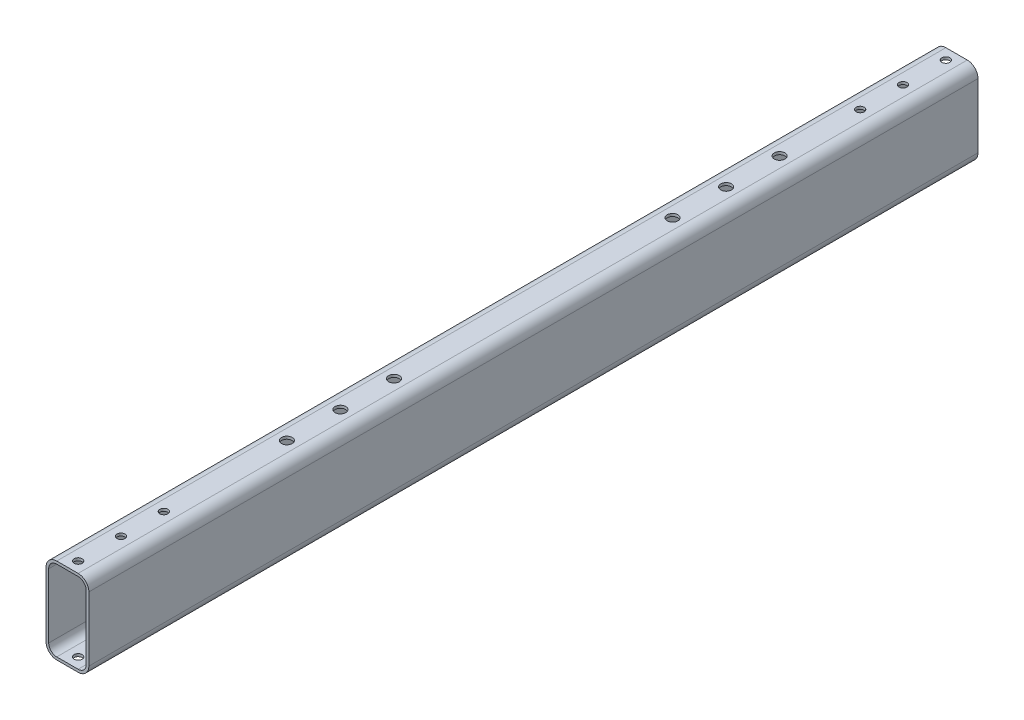
SolidWorks part; units mm, degrees
material "6061-T6 (SS)"
ref_plane "Front Plane" through (0, 0, 0) normal (0, 0, 1) x (1, 0, 0)
ref_plane "Top Plane" through (0, 0, 0) normal (0, 1, 0) x (1, 0, 0)
ref_plane "Right Plane" through (0, 0, 0) normal (1, 0, 0) x (0, 0, -1)
sketch "Sketch1" plane through (0, 0, 0) normal (0, 0, 1) x (1, 0, 0)
  line L1 (-6.35, -25.4) -> (6.35, -25.4)
  line L2 (-12.7, -19.05) -> (-12.7, 19.05)
  line L3 (-6.35, 25.4) -> (6.35, 25.4)
  line L4 (12.7, -19.05) -> (12.7, 19.05)
  line L5 (-12.7, -25.4) -> (12.7, 25.4) construction
  line L6 (-12.7, 25.4) -> (12.7, -25.4) construction
  arc A0 (-12.7, -19.05) -> (-6.35, -25.4) centre (-6.35, -19.05) ccw
  arc A1 (6.35, -25.4) -> (12.7, -19.05) centre (6.35, -19.05) ccw
  arc A2 (6.35, 25.4) -> (12.7, 19.05) centre (6.35, 19.05) cw
  arc A3 (-12.7, 19.05) -> (-6.35, 25.4) centre (-6.35, 19.05) cw
  point P0 (0, 0)
  dimension "D3" = 6.35
  dimension "D1" = 50.8
  dimension "D2" = 25.4
extrude "Extrude-Thin1" add sketch "Sketch1" along normal blind 527.05 thin thin type one direction reverse wall 1.5875
hole_wizard "3/16 (0.1875) Diameter Hole1" positions "3DSketch1" profile "Sketch3" hole size "3/16" standard "ANSI Inch" end condition through all
sketch3d "3DSketch1"
  line L1 (6.35, 25.4, 0) -> (-6.35, 25.4, 0) construction
  line L6 (0, 25.4, 527.05) -> (0, 25.4, 0) construction
  line L7 (6.35, 25.4, 527.05) -> (-6.35, 25.4, 527.05) construction
  point P57 (0, 25.4, 6.35)
  point P59 (0, 25.4, 31.75)
  point P61 (0, 25.4, 57.15)
  point P63 (0, 25.4, 495.3)
  point P65 (0, 25.4, 469.9)
  point P67 (0, 25.4, 520.7)
  dimension "D1" = 25.4
  dimension "D2" = 25.4
  dimension "D3" = 6.35
  dimension "D4" = 25.4
  dimension "D5" = 25.4
  dimension "D6" = 6.35
sketch "Sketch3" plane through (0, 25.4, 520.7) normal (1, 0, 0) x (0, 0, 1)
  line L0 (0, 0) -> (0, 50.8)
  line L1 (0, 50.8) -> (2.3812, 50.8)
  line L2 (2.3812, 50.8) -> (2.3812, 0)
  line L5 (2.3812, 0) -> (0, 0)
  line L11 (0, -6.35) -> (0, 107.95) construction
  dimension "Thru Hole Dia." = 4.7625
  dimension "Thru Hole Depth" = 50.8
hole_wizard "3/16 (0.195) Diameter Hole1" positions "Sketch4" profile "Sketch5" hole size "3/16" standard "ANSI Inch" end condition up to next
sketch "Sketch4" plane through (0, -25.4, 0) normal (0, -1, 0) x (-1, 0, 0)
  point P28 (3.175, -69.85)
  point P31 (-3.175, -95.25)
  point P34 (3.175, -120.65)
  point P37 (-3.175, -146.05)
  point P40 (3.175, -171.45)
  point P43 (3.175, -323.85)
  point P46 (-3.175, -349.25)
  point P49 (3.175, -374.65)
  point P52 (-3.175, -400.05)
  point P55 (3.175, -425.45)
sketch "Sketch5" plane through (-3.175, -25.4, 69.85) normal (1, 0, 0) x (0, 0, -1)
  line L0 (0, 0) -> (0, 1.5875)
  line L1 (0, 1.5875) -> (2.4765, 1.5875)
  line L2 (2.4765, 1.5875) -> (2.4765, 0)
  line L5 (2.4765, 0) -> (0, 0)
  line L11 (0, -6.35) -> (0, 107.95) construction
  dimension "Thru Hole Dia." = 4.953
  dimension "Thru Hole Depth" = 1.5875
hole_wizard "1/4 (0.25) Diameter Hole1" positions "Sketch7" profile "Sketch6" hole size "1/4" standard "ANSI Inch"
sketch "Sketch7" plane through (0, 25.4, 0) normal (0, 1, 0) x (1, 0, 0)
  point P0 (0, -104.85)
  point P3 (0, -136.6)
  point P6 (0, -168.35)
  point P9 (0, -396.9748)
  point P12 (0, -365.2248)
  point P15 (0, -333.4748)
sketch "Sketch6" plane through (0, 25.4, 104.85) normal (1, 0, 0) x (0, 0, 1)
  line L0 (0, 0) -> (0, 27.3077)
  line L1 (0, 27.3077) -> (3.175, 25.4)
  line L2 (3.175, 25.4) -> (3.175, 0)
  line L5 (3.175, 0) -> (0, 0)
  line L10 (0, 27.3077) -> (-3.175, 25.4) construction
  line L11 (0, -6.35) -> (0, 107.95) construction
  dimension "Hole Dia." = 6.35
  dimension "Hole Depth" = 25.4
  dimension "Drill Angle" = 118
